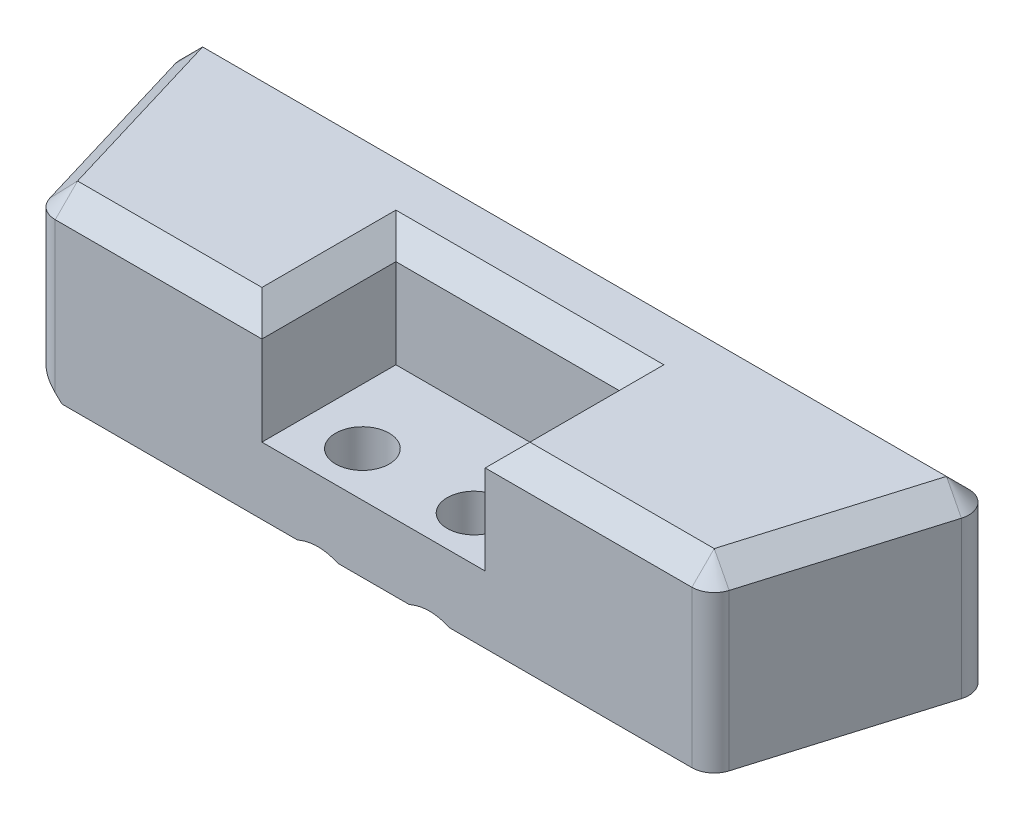
SolidWorks part; units mm, degrees
material "Liga 1060"
ref_plane "Plano frontal" through (0, 0, 0) normal (0, 0, 1) x (1, 0, 0)
ref_plane "Plano superior" through (0, 0, 0) normal (0, 1, 0) x (1, 0, 0)
ref_plane "Plano direito" through (0, 0, 0) normal (1, 0, 0) x (0, 0, -1)
sketch "Esboço2" plane through (0, 0, 0) normal (0, 1, 0) x (1, 0, 0)
  line L4 (-0.2138, 0.7127) -> (-2.6138, 8.7127)
  line L6 (32.6138, 8.7127) -> (30.2138, 0.7127)
  line L7 (29.256, 0) -> (0.744, 0)
  line L8 (-1.656, 10) -> (31.656, 10)
  arc A1 (30.2138, 0.7127) -> (29.256, 0) centre (29.256, 1) cw
  arc A2 (-0.2138, 0.7127) -> (0.744, 0) centre (0.744, 1) ccw
  arc A5 (32.6138, 8.7127) -> (31.656, 10) centre (31.656, 9) ccw
  arc A6 (-2.6138, 8.7127) -> (-1.656, 10) centre (-1.656, 9) cw
  point P2 (15, 10)
  point P6 (15, 0)
  point P7 (33, 10)
  point P10 (30, 0)
  point P13 (0, 0)
  point P18 (-3, 10)
  dimension "D4" = 1
  dimension "D5" = 36
  dimension "D2" = 10
  dimension "D3" = 1
  dimension "D1" = 30
extrude "Ressalto-extrusão2" add sketch "Esboço2" along normal blind 8
sketch "Esboço4" plane through (0, 8, 0) normal (0, 1, 0) x (1, 0, 0)
  line L0 (15, 0) -> (15, 2.6) construction
  line L1 (0.744, 0) -> (29.256, 0) construction
  line L2 (6.5, 2.6) -> (23.5, 2.6) construction
  line L4 (20.9, 0) -> (26.1, 0)
  line L5 (20.9, 0) -> (20.9, 5.2)
  line L6 (20.9, 5.2) -> (26.1, 5.2)
  line L7 (26.1, 0) -> (26.1, 5.2)
  line L8 (20.9, 0) -> (26.1, 5.2) construction
  line L9 (20.9, 5.2) -> (26.1, 0) construction
  line L10 (9.1, 0) -> (3.9, 0)
  line L11 (9.1, 0) -> (9.1, 5.2)
  line L12 (9.1, 5.2) -> (3.9, 5.2)
  line L13 (3.9, 0) -> (3.9, 5.2)
  line L14 (9.1, 0) -> (3.9, 5.2) construction
  line L15 (9.1, 5.2) -> (3.9, 0) construction
  point P7 (15, 2.6)
  dimension "D1" = 17
  dimension "D2" = 2.6
  dimension "D3" = 5.2
  dimension "D4" = 5.2
sketch "Esboço5" plane through (0, 8, 0) normal (0, 1, 0) x (1, 0, 0)
  line L0 (15, 0) -> (15, 6) construction
  line L1 (0.744, 0) -> (29.256, 0) construction
  line L2 (10, 6) -> (20, 6)
  line L3 (10, 6) -> (10, 0)
  line L4 (10, 0) -> (20, 0)
  line L5 (20, 0) -> (20, 6)
  point P7 (15, 6)
  dimension "D1" = 10
  dimension "D2" = 6
extrude "Corte-extrusão1" cut sketch "Esboço5" against normal blind 5
sketch "Esboço6" plane through (0, 0, 0) normal (0, -1, 0) x (1, 0, 0)
  line L0 (12.5, 0) -> (17.5, 0)
  line L2 (0.744, 0) -> (29.256, 0) construction
  line L3 (12.5, 0) -> (12.5, -2)
  line L4 (20, -6) -> (10, -6) construction
  line L6 (12.5, -2) -> (17.5, -2)
  point P5 (15, 0)
  point P6 (15, 0)
  dimension "D1" = 5
  dimension "D2" = 4
hole_wizard "Escareado para parafuso com cabeça escareada chata de M21" positions "3DSketch1" profile "Esboço8" countersink size "M2" standard "ISO" end condition through all
sketch3d "3DSketch1"
  point P0 (17.5, 0, -2)
  point P19 (12.5, 0, -2)
sketch "Esboço8" plane through (17.5, 0, -2) normal (1, 0, 0) x (0, 0, -1)
  line L0 (0, 0) -> (0, 8)
  line L1 (0, 8) -> (1.2, 8)
  line L2 (1.2, 8) -> (1.2, 1)
  line L3 (1.2, 1) -> (2.2, 0)
  line L5 (2.2, 0) -> (0, 0)
  line L6 (-1.2, 1) -> (-2.2, 0) construction
  line L11 (0, -6.35) -> (0, 107.95) construction
  dimension "Thru Hole Dia." = 2.4
  dimension "Thru Hole Depth" = 8
  dimension "Near C'Sink Dia." = 4.4
  dimension "Near C'Sink Angle" = 90
chamfer "Chanfro1" distance 1 angle 45 13 edges at (15, 8, -6) (10, 8, -3) (5.372, 8, 0) (0.1471, 8, -0.1977) (-1.4138, 8, -4.7127) (-2.4583, 8, -9.5969) (15, 8, -10) (32.4583, 8, -9.5969) (31.4138, 8, -4.7127) (29.8529, 8, -0.1977) (24.628, 8, 0) (20, 8, -3) (-1.4138, 0, -4.7127)
